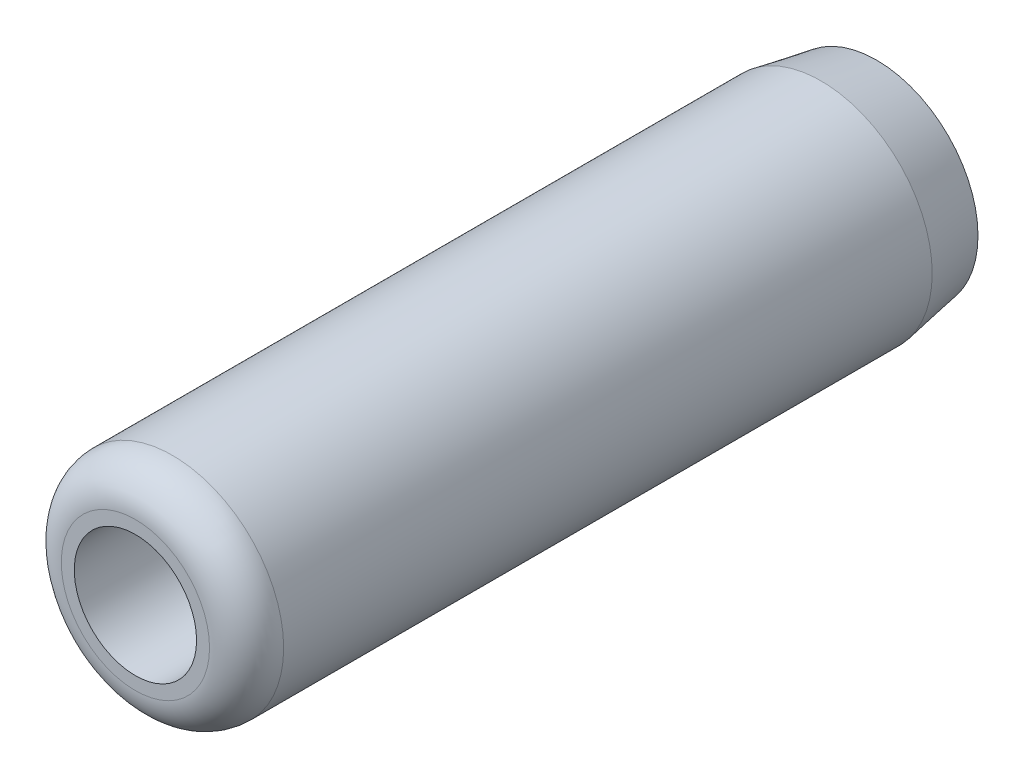
SolidWorks part; units mm, degrees
material "S45C"
ref_plane "正面" through (0, 0, 0) normal (0, 0, 1) x (1, 0, 0)
ref_plane "平面" through (0, 0, 0) normal (0, 1, 0) x (1, 0, 0)
ref_plane "右側面" through (0, 0, 0) normal (1, 0, 0) x (0, 0, -1)
sketch "ｽｹｯﾁ1" plane through (0, 0, 0) normal (1, 0, 0) x (0, 0, -1)
  line L0 (0, 0) -> (129.8709, 0) construction
  line L1 (0, 0) -> (0, 2)
  line L2 (1, 3) -> (18.5, 3)
  line L3 (18.5, 3) -> (20, 2.7355)
  line L4 (20, 2.7355) -> (20, 0)
  line L5 (20, 0) -> (0, 0)
  arc A0 (0, 2) -> (1, 3) centre (1, 2) cw
  point P6 (16.9867, 3)
  dimension "D5" = 1
  dimension "D1" = 10
  dimension "D2" = 20
  dimension "D3" = 6
  dimension "D4" = 1.5
revolve "回転1" add sketch "ｽｹｯﾁ1" angle 360 about L0
hole_wizard "M4 ねじ穴1" positions "ｽｹｯﾁ2" profile "ｽｹｯﾁ3" tap size "M4" standard "JIS" end condition through all
sketch "ｽｹｯﾁ2" plane through (0, 0, 0) normal (0, 0, 1) x (1, 0, 0)
  point P0 (0, 0)
sketch "ｽｹｯﾁ3" plane through (0, 0, 0) normal (1, 0, 0) x (0, -1, 0)
  line L0 (0, 0) -> (0, 20)
  line L1 (0, 20) -> (1.65, 20)
  line L2 (1.65, 20) -> (1.65, 0)
  line L5 (1.65, 0) -> (0, 0)
  line L11 (0, -6.35) -> (0, 107.95) construction
  dimension "次ｻｰﾌｪｽまでのねじ下穴ﾄﾞﾘﾙ直径" = 3.3
  dimension "次ｻｰﾌｪｽまでのねじ下穴ﾄﾞﾘﾙの深さ" = 20
cosmetic thread "穴のねじ山1"
